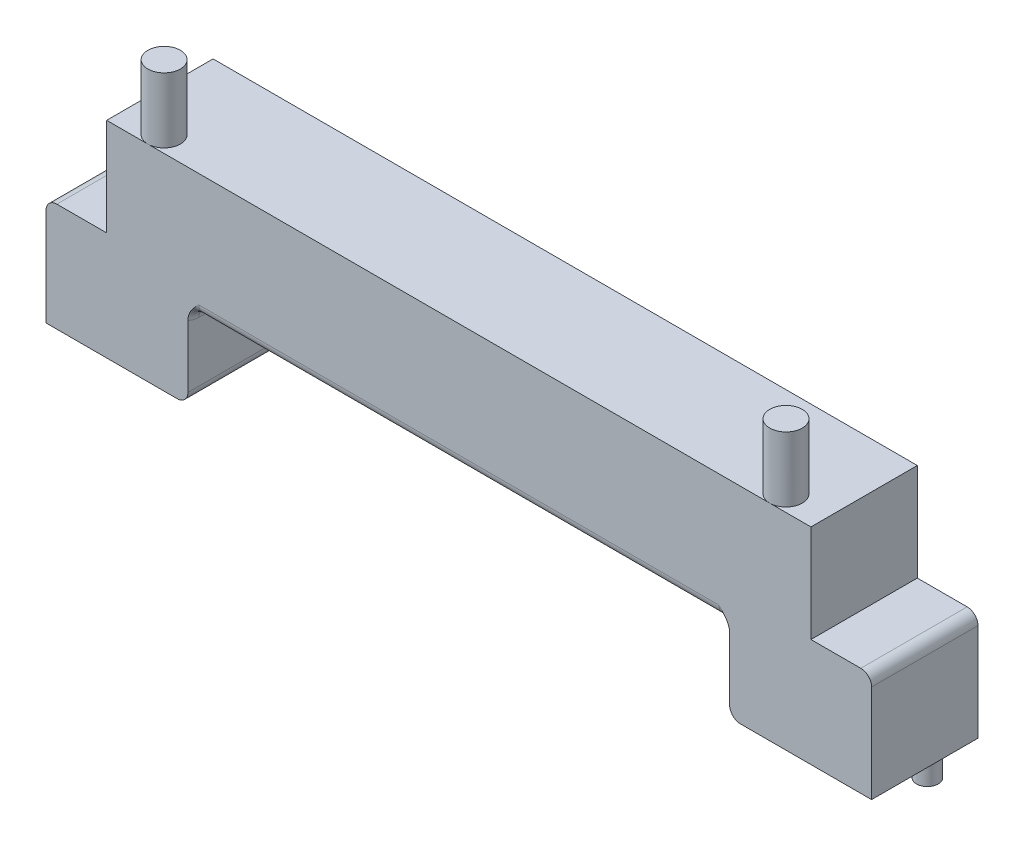
SolidWorks part; units mm, degrees
ref_plane "Front Plane" through (0, 0, 0) normal (0, 0, 1) x (1, 0, 0)
ref_plane "Top Plane" through (0, 0, 0) normal (0, 1, 0) x (1, 0, 0)
ref_plane "Right Plane" through (0, 0, 0) normal (1, 0, 0) x (0, 0, -1)
sketch "Sketch2" plane through (0, 0, 0) normal (0, 0, 1) x (1, 0, 0)
  line L0 (0, 10) -> (5.6, 10)
  line L1 (5.6, 19) -> (70.6, 19)
  line L2 (0, 10) -> (0, 0)
  line L3 (0, 0) -> (13.1, 0)
  line L4 (76.2, 10) -> (76.2, 0)
  line L5 (5.6, 0) -> (13.1, 0) construction
  line L6 (63.1, 0) -> (76.2, 0)
  line L7 (5.6, 10) -> (5.6, 19)
  line L8 (70.6, 19) -> (70.6, 10)
  line L9 (70.6, 10) -> (76.2, 10)
  line L11 (13.1, 0) -> (13.1, 7.5)
  line L12 (13.1, 7.5) -> (63.1, 7.5)
  line L13 (63.1, 0) -> (63.1, 7.5)
  line L16 (63.1, 0) -> (76.2, 0) construction
  point P0 (0, 0)
  point P4 (38.1, 0)
  dimension "D1" = 76.2
  dimension "D2" = 65
  dimension "D3" = 10
  dimension "D4" = 9
  dimension "D5" = 50
  dimension "D6" = 7.5
extrude "Boss-Extrude1" add sketch "Sketch2" against normal blind 9.82
sketch "Sketch3" plane through (0, 19, 0) normal (0, 1, 0) x (1, 0, 0)
  line L0 (5.6, 9.82) -> (5.6, 0) construction
  line L2 (70.6, 0) -> (5.6, 0) construction
  line L3 (38.1, 0) -> (38.1, 9.82) construction
  line L4 (70.6, 9.82) -> (5.6, 9.82) construction
  circle A0 centre (9.4, 1.5) radius 1.5
  circle A1 centre (66.8, 1.5) radius 1.5
  dimension "D3" = 3
  dimension "D1" = 3.8
  dimension "D2" = 1.5
extrude "Boss-Extrude2" add sketch "Sketch3" along normal blind 6
sketch "Sketch5" plane through (0, 0, 0) normal (0, -1, 0) x (1, 0, 0)
  line L0 (63.1, -9.82) -> (76.2, -9.82) construction
  line L1 (76.2, -9.82) -> (76.2, 0) construction
  line L2 (38.1, 0) -> (38.1, -9.82) construction
  line L3 (13.1, 0) -> (63.1, 0) construction
  line L4 (13.1, -9.82) -> (63.1, -9.82) construction
  circle A0 centre (73.025, -8.32) radius 1
  circle A1 centre (3.175, -8.32) radius 1
  dimension "D1" = 2
  dimension "D2" = 1.5
  dimension "D3" = 3.175
extrude "Boss-Extrude3" add sketch "Sketch5" along normal blind 4
fillet "Fillet1" radius 1 1 edges at (38.1, 7.5, 0)
fillet "Fillet3" radius 1 8 edges at (13.1, 7.7929, -0.2929) (63.1, 7.7929, -0.2929) (13.1, 7.5, -5.41) (63.1, 7.5, -5.41) (63.1, 0, -4.91) (13.1, 0, -4.91) (0, 10, -4.91) (76.2, 10, -4.91)
